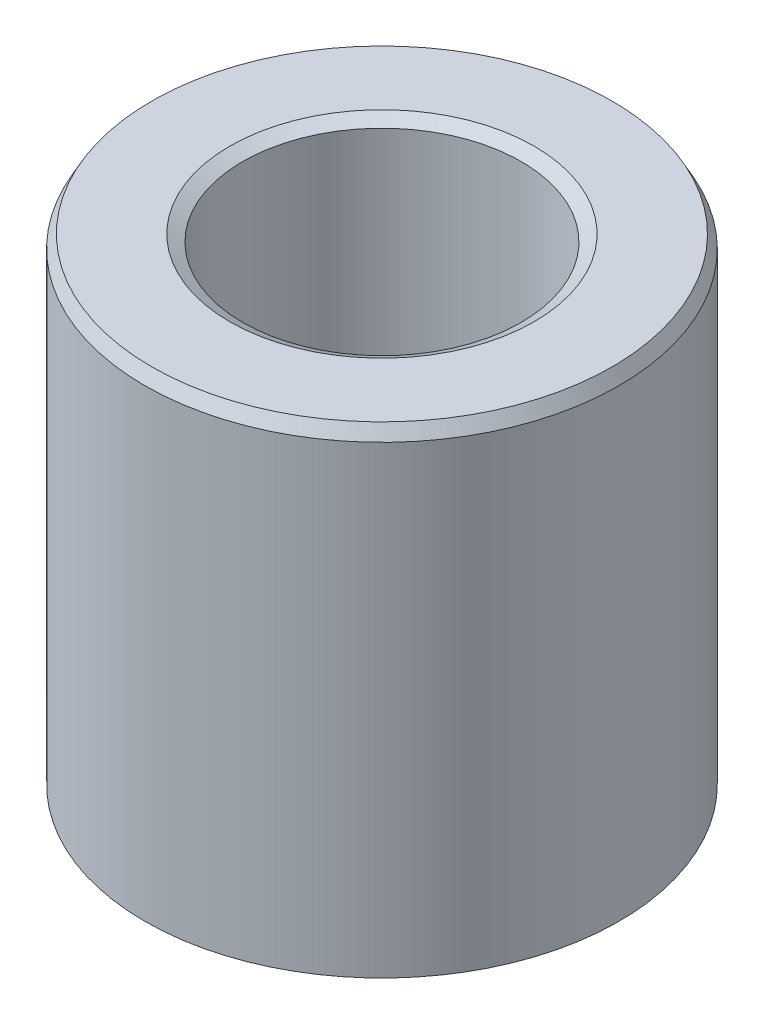
SolidWorks part; units mm, degrees
ref_plane "Front Plane" through (0, 0, 0) normal (0, 0, 1) x (1, 0, 0)
ref_plane "Top Plane" through (0, 0, 0) normal (0, 1, 0) x (1, 0, 0)
ref_plane "Right Plane" through (0, 0, 0) normal (1, 0, 0) x (0, 0, -1)
sketch "Sketch1" plane through (0, 0, 0) normal (0, 1, 0) x (1, 0, 0)
  circle A0 centre (0, 0) radius 22.5
  dimension "SLEEVE_OD" = 45
extrude "Boss-Extrude1" add sketch "Sketch1" along normal blind 45.893
sketch "Sketch2" plane through (0, 0, 0) normal (0, 1, 0) x (1, 0, 0)
  circle A0 centre (0, 0) radius 13.2207
  dimension "BORE_D" = 26.4414
extrude "Cut-Extrude1" cut sketch "Sketch2" along normal through all
chamfer "Chamfer1" distance 1.2158 angle 28.411 4 edges at (0, 45.893, 13.2207) (0, 0, 13.2207) (0, 0, 22.5) (0, 45.893, 22.5) first distance on face at (0, 45.893, 13.2207) first distance on face at (0, 0, 13.2207) first distance on face at (0, 45.893, 22.5)
